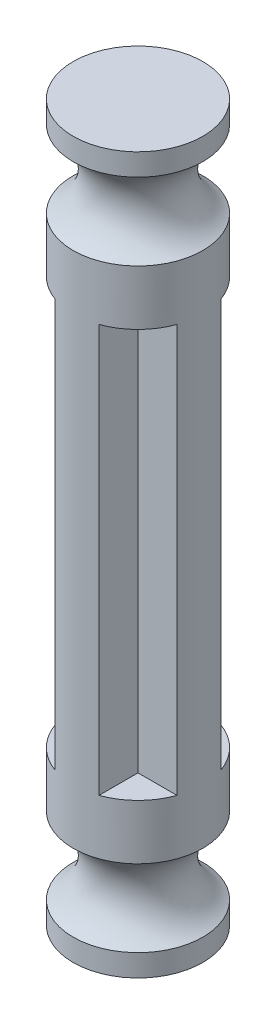
SolidWorks part; units mm, degrees
ref_plane "前视基准面" through (0, 0, 0) normal (0, 0, 1) x (1, 0, 0)
ref_plane "上视基准面" through (0, 0, 0) normal (0, 1, 0) x (1, 0, 0)
ref_plane "右视基准面" through (0, 0, 0) normal (1, 0, 0) x (0, 0, -1)
sketch "草图1" plane through (0, 0, 0) normal (0, 1, 0) x (1, 0, 0)
  line L0 (1, 1) -> (1, 2.7753)
  line L7 (1, 1) -> (2.7753, 1)
  line L8 (1, -1) -> (2.7753, -1)
  line L9 (1, -1) -> (1, -2.7753)
  line L10 (-1, -1) -> (-1, -2.7753)
  line L11 (-1, -1) -> (-2.7753, -1)
  line L12 (-1, 1) -> (-2.7753, 1)
  line L13 (-1, 1) -> (-1, 2.7753)
  arc A0 (-2.7753, 1) -> (-2.7753, -1) centre (0, 0) ccw
  arc A1 (-1, -2.7753) -> (1, -2.7753) centre (0, 0) ccw
  arc A2 (2.7753, -1) -> (2.7753, 1) centre (0, 0) ccw
  arc A3 (1, 2.7753) -> (-1, 2.7753) centre (0, 0) ccw
  dimension "D1" = 5.9
  dimension "D2" = 2
  dimension "D3" = 2
  dimension "D4" = 2
  dimension "D5" = 2
  dimension "D6" = 1
  dimension "D7" = 1
  dimension "D8" = 1
  dimension "D9" = 1
extrude "凸台-拉伸2" add sketch "草图1" along normal blind 18.56
sketch "草图3" plane through (0, 0, 0) normal (1, 0, 0) x (0, 0, -1)
  line L0 (0, 18.56) -> (0, 25.56)
  line L1 (1, 18.56) -> (-1, 18.56) construction
  line L2 (0, 25.56) -> (2.95, 25.56)
  line L3 (0, 18.56) -> (2.95, 18.56)
  line L4 (2.95, 18.56) -> (2.95, 21.06)
  line L5 (2.95, 25.56) -> (2.95, 24.56)
  line L6 (0, 0) -> (0, -7)
  line L7 (0, -7) -> (2.95, -7)
  line L8 (0, 0) -> (2.95, 0)
  line L9 (2.95, 0) -> (2.95, -2.5)
  line L10 (2.95, -7) -> (2.95, -6)
  arc A0 (2.95, 24.56) -> (2.95, 21.06) centre (3.9182, 22.81) ccw
  arc A1 (2.95, -2.5) -> (2.95, -6) centre (3.9182, -4.25) ccw
  dimension "D5" = 1
  dimension "D4" = 2
  dimension "D9" = 2
  dimension "D1" = 2.95
  dimension "D2" = 7
  dimension "D3" = 2.5
  dimension "D6" = 7
  dimension "D7" = 2.5
  dimension "D8" = 1
revolve "旋转3" add sketch "草图3" angle 360 about L6
